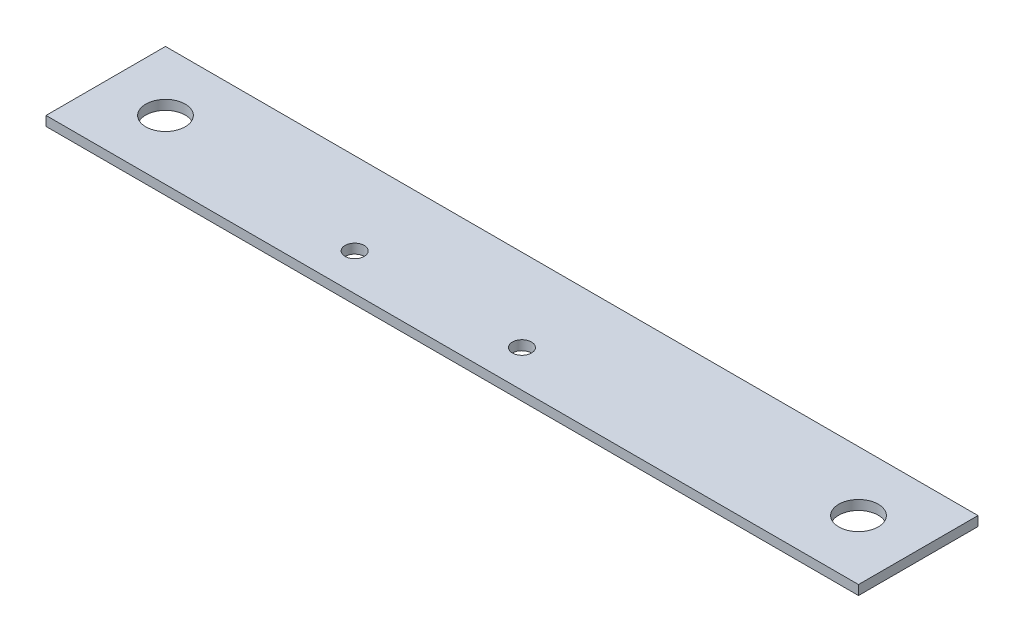
SolidWorks part; units mm, degrees
ref_plane "Front Plane" through (0, 0, 0) normal (0, 0, 1) x (1, 0, 0)
ref_plane "Top Plane" through (0, 0, 0) normal (0, 1, 0) x (1, 0, 0)
ref_plane "Right Plane" through (0, 0, 0) normal (1, 0, 0) x (0, 0, -1)
sketch "Sketch1" plane through (0, 0, 0) normal (0, 1, 0) x (1, 0, 0)
  line L1 (-85, 12.5) -> (85, 12.5)
  line L2 (-85, 12.5) -> (-85, -12.5)
  line L3 (-85, -12.5) -> (85, -12.5)
  line L4 (85, 12.5) -> (85, -12.5)
  line L5 (-85, 12.5) -> (85, -12.5) construction
  line L6 (-85, -12.5) -> (85, 12.5) construction
  circle A0 centre (-10.6801, 3.3392) radius 4.5
  circle A1 centre (-10.6585, -3.6607) radius 14
  circle A2 centre (-28.1585, -4.7634) radius 2
  circle A3 centre (6.8415, -4.7634) radius 2
  circle A4 centre (72.5, 0) radius 4.125
  point P0 (0, 0)
  point P17 (85, 0)
  dimension "D3" = 12.5
  dimension "D4" = 4
  dimension "D5" = 4
  dimension "D6" = 8.25
  dimension "D1" = 25
  dimension "D2" = 170
extrude "Boss-Extrude1" add sketch "Sketch1" along normal blind 2 contours A1 L3 L4 L1 L2 A4 A3 A2 | L3 A1 A0 | A0 region at (0, 0, -10.7817) region at (-10.6556, 0, 2.8007)
sketch "Sketch2" plane through (0, 2, 0) normal (0, 1, 0) x (1, 0, 0)
  line L0 (-85, 12.5) -> (-85, -12.5) construction
  circle A0 centre (-72.5, 0) radius 4.125
  circle A1 centre (-72.5, 0) radius 20 construction
  circle A2 centre (-42.5, 0) radius 10 construction
  dimension "D1" = 8.25
  dimension "D2" = 12.5
extrude "Cut-Extrude1" cut sketch "Sketch2" against normal through all
